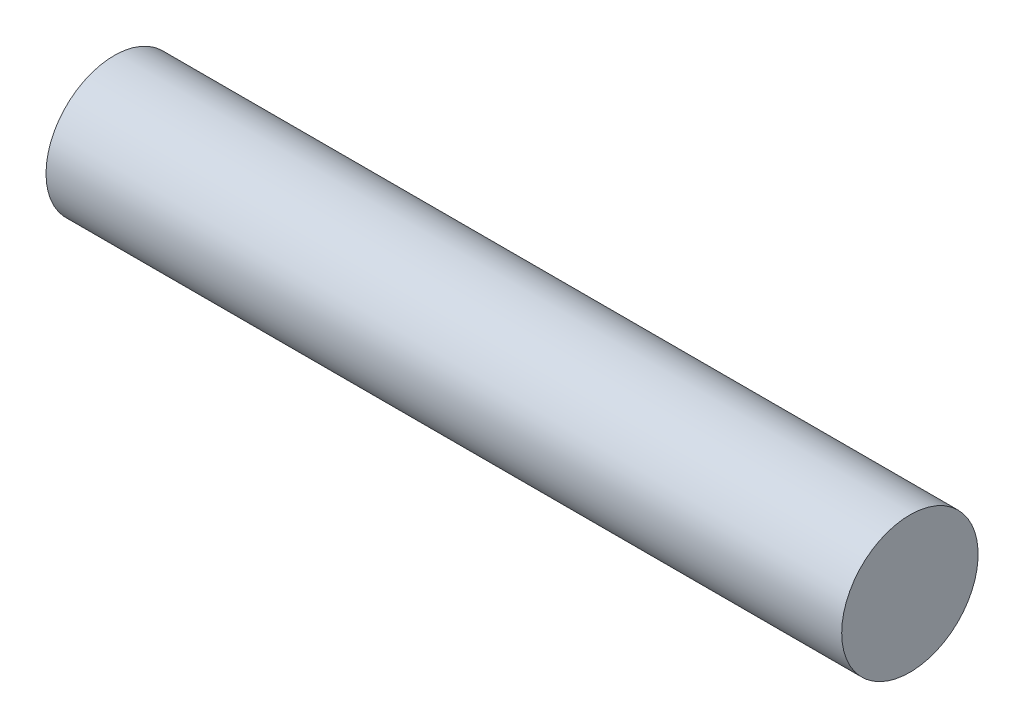
SolidWorks part; units mm, degrees
ref_plane "Front Plane" through (0, 0, 0) normal (0, 0, 1) x (1, 0, 0)
ref_plane "Top Plane" through (0, 0, 0) normal (0, 1, 0) x (1, 0, 0)
ref_plane "Right Plane" through (0, 0, 0) normal (1, 0, 0) x (0, 0, -1)
sketch "Sketch1" plane through (0, 0, 0) normal (0, 0, 1) x (1, 0, 0)
  line L0 (0, 0) -> (34.9915, 0) construction
  line L1 (0, 0) -> (0, 3)
  line L2 (0, 3) -> (34.9915, 3)
  line L7 (34.9915, 3) -> (34.9915, 0)
  line L8 (0, 0) -> (34.9915, 0)
  point P3 (0, 0)
  point P6 (43.8258, 3)
  dimension "D1" = 34.9915
  dimension "D4" = 6
revolve "Revolve1" add sketch "Sketch1" angle 360 about L0
